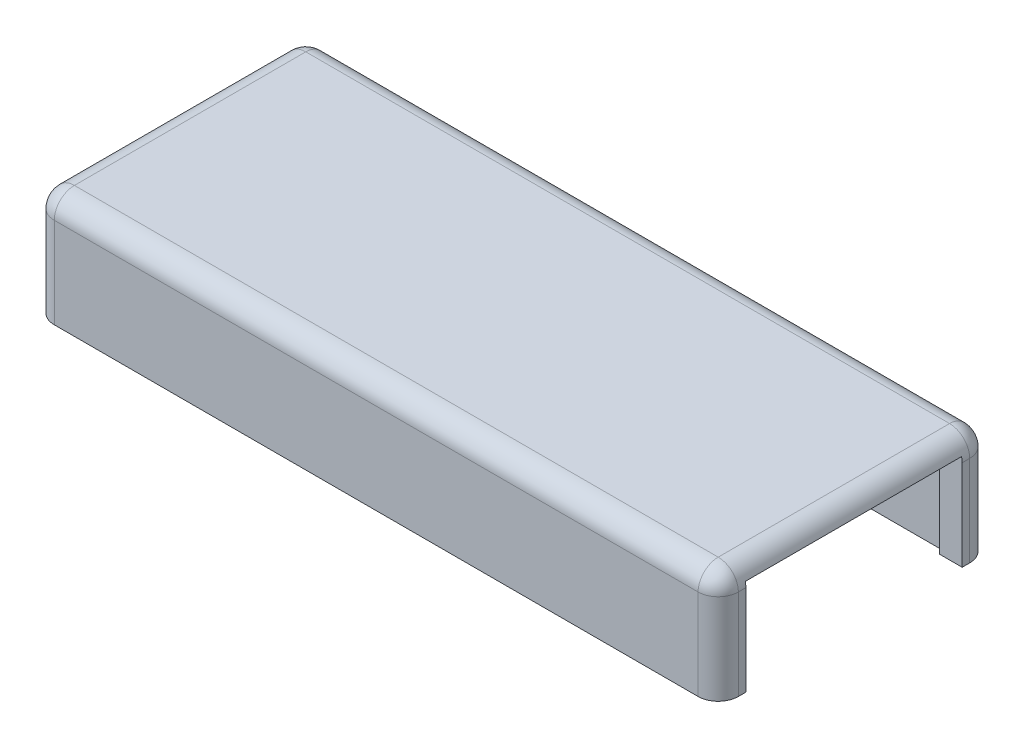
SolidWorks part; units mm, degrees
ref_plane "Спереди" through (0, 0, 0) normal (0, 0, 1) x (1, 0, 0)
ref_plane "Сверху" through (0, 0, 0) normal (0, 1, 0) x (1, 0, 0)
ref_plane "Справа" through (0, 0, 0) normal (1, 0, 0) x (0, 0, -1)
sketch "Эскиз1" plane through (0, 0, 0) normal (0, 1, 0) x (1, 0, 0)
  line L1 (-34, 13.5) -> (34, 13.5)
  line L2 (-34, 13.5) -> (-34, -13.5)
  line L3 (-34, -13.5) -> (34, -13.5)
  line L4 (34, 13.5) -> (34, -13.5)
  line L5 (-34, 13.5) -> (34, -13.5) construction
  line L6 (-34, -13.5) -> (34, 13.5) construction
  point P0 (0, 0)
  dimension "D1" = 68
  dimension "D2" = 27
extrude "Бобышка-Вытянуть1" add sketch "Эскиз1" along normal blind 11
sketch "Эскиз2" plane through (0, 0, 0) normal (0, -1, 0) x (1, 0, 0)
  line L1 (31.75, -11.25) -> (-31.75, -11.25)
  line L2 (31.75, -11.25) -> (31.75, 11.25)
  line L3 (31.75, 11.25) -> (-31.75, 11.25)
  line L4 (-31.75, -11.25) -> (-31.75, 11.25)
  line L5 (31.75, -11.25) -> (-31.75, 11.25) construction
  line L6 (31.75, 11.25) -> (-31.75, -11.25) construction
  point P0 (0, 0)
  dimension "D1" = 22.5
  dimension "D2" = 63.5
extrude "Вырез-Вытянуть1" cut sketch "Эскиз2" against normal offset from surface (9.5 mm away) 1.5 up to face at (0, 11, 0)
sketch "Эскиз3" plane through (-34, 0, 0) normal (-1, 0, 0) x (0, 0, 1)
  line L0 (0, 0) -> (0, 15.0821) construction
  line L1 (-13.5, 0) -> (13.5, 0) construction
  line L2 (-3.3, 2.1) -> (3.3, 2.1) construction
  line L3 (-4.6, 2.1) -> (-4.6, 0)
  line L4 (-4.6, 0) -> (4.6, 0)
  line L6 (-3.3, 3.4) -> (3.3, 3.4)
  line L7 (4.6, 2.1) -> (4.6, 0)
  arc A1 (-3.3, 3.4) -> (-4.6, 2.1) centre (-3.3, 2.1) ccw
  arc A2 (3.3, 3.4) -> (4.6, 2.1) centre (3.3, 2.1) cw
  point P7 (0, 2.1)
  point P12 (0, 0)
  point P14 (0, 3.4)
  dimension "D2" = 1.3
  dimension "D1" = 9.2
  dimension "D3" = 3.4
extrude "Вырез-Вытянуть2" cut sketch "Эскиз3" against normal up to surface (2.25 mm away) up to face at (-31.75, 4.75, 0)
sketch "Эскиз4" plane through (34, 0, 0) normal (1, 0, 0) x (0, 0, -1)
  line L0 (0, 0) -> (0, 16.049) construction
  line L1 (-13.5, 0) -> (13.5, 0) construction
  line L3 (10.75, 9.5) -> (-10.75, 9.5)
  line L4 (10.75, 9.5) -> (10.75, 0)
  line L5 (10.75, 0) -> (-10.75, 0)
  line L6 (-10.75, 9.5) -> (-10.75, 0)
  line L7 (10.75, 9.5) -> (-10.75, 0) construction
  line L8 (10.75, 0) -> (-10.75, 9.5) construction
  point P4 (0, 4.75)
  dimension "D1" = 21.5
  dimension "D2" = 9.5
extrude "Вырез-Вытянуть3" cut sketch "Эскиз4" against normal up to surface (2.25 mm away) up to face at (31.75, 4.75, 0)
sketch "Эскиз5" plane through (0, 9.5, 0) normal (0, -1, 0) x (1, 0, 0)
  line L0 (0, 0) -> (-47.1897, 0) construction
  line L1 (-21.5, -9) -> (-21.5, 9) construction
  line L2 (-19.5, -9) -> (-19.5, -11.25)
  line L3 (-31.75, -11.25) -> (31.75, -11.25) construction
  line L4 (-19.5, -11.25) -> (-23.5, -11.25)
  line L5 (-23.5, -11.25) -> (-23.5, -9)
  line L6 (-23.5, 11.25) -> (-23.5, 9)
  line L7 (-19.5, 11.25) -> (-23.5, 11.25)
  line L8 (-19.5, 9) -> (-19.5, 11.25)
  arc A0 (-19.5, -9) -> (-23.5, -9) centre (-21.5, -9) ccw
  arc A1 (-19.5, 9) -> (-23.5, 9) centre (-21.5, 9) cw
  point P5 (-21.5, 0)
  dimension "D3" = 2
  dimension "D1" = 21.5
  dimension "D2" = 18
extrude "Бобышка-Вытянуть2" add sketch "Эскиз5" along normal up to surface (9.5 mm away) up to face at (0, 0, -10.025)
sketch "Эскиз6" plane through (0, 9.5, 0) normal (0, -1, 0) x (1, 0, 0)
  line L0 (0, 0) -> (37.8557, 0) construction
  line L1 (23, -11) -> (23, 11) construction
  line L2 (23.7, -11) -> (23.7, -11.25)
  line L3 (-19.5, -11.25) -> (31.75, -11.25) construction
  line L4 (23.7, -11.25) -> (22.3, -11.25)
  line L5 (22.3, -11.25) -> (22.3, -11)
  line L6 (22.3, 11.25) -> (22.3, 11)
  line L7 (23.7, 11.25) -> (22.3, 11.25)
  line L8 (23.7, 11) -> (23.7, 11.25)
  arc A0 (23.7, -11) -> (22.3, -11) centre (23, -11) ccw
  arc A1 (23.7, 11) -> (22.3, 11) centre (23, 11) cw
  point P5 (23, 0)
  dimension "D3" = 0.7
  dimension "D1" = 23
  dimension "D2" = 22
extrude "Бобышка-Вытянуть3" add sketch "Эскиз6" along normal up to surface (9.5 mm away) up to face at (-7.1667, 0, 9.8917)
sketch "Эскиз7" plane through (0, 0, 0) normal (0, -1, 0) x (1, 0, 0)
  line L0 (0, 0) -> (-43.0608, 0) construction
  line L1 (-21.5, -9) -> (-21.5, 9) construction
  circle A0 centre (-21.5, -9) radius 1
  circle A1 centre (-21.5, 9) radius 1
  point P6 (-21.5, 0)
  dimension "D1" = 2
extrude "Вырез-Вытянуть4" cut sketch "Эскиз7" against normal up to surface (9.5 mm away) up to face at (5.9792, 9.5, 0)
fillet "Скругление1" radius 2 8 edges at (34, 11, 0) (34, 5.5, 13.5) (0, 11, 13.5) (-34, 5.5, 13.5) (-34, 11, 0) (-34, 5.5, -13.5) (0, 11, -13.5) (34, 5.5, -13.5)
